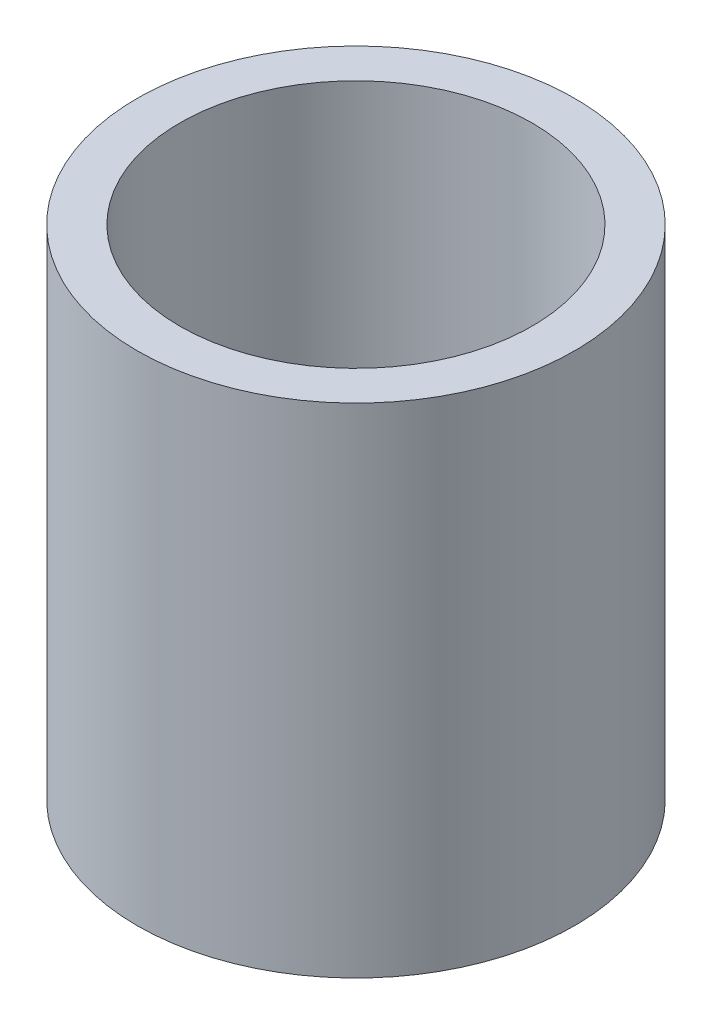
SolidWorks part; units mm, degrees
ref_plane "Front Plane" through (0, 0, 0) normal (0, 0, 1) x (1, 0, 0)
ref_plane "Top Plane" through (0, 0, 0) normal (0, 1, 0) x (1, 0, 0)
ref_plane "Right Plane" through (0, 0, 0) normal (1, 0, 0) x (0, 0, -1)
sketch "Sketch1" plane through (0, 0, 0) normal (0, 1, 0) x (1, 0, 0)
  circle A0 centre (0, 0) radius 27.5
  dimension "SLEEVE_OD" = 55
extrude "Boss-Extrude1" add sketch "Sketch1" along normal blind 62.6106
sketch "Sketch2" plane through (0, 0, 0) normal (0, 1, 0) x (1, 0, 0)
  circle A0 centre (0, 0) radius 22.1463
  dimension "BORE_D" = 44.2925
extrude "Cut-Extrude1" cut sketch "Sketch2" along normal through all
chamfer "Chamfer1" distance 3.4172 angle 60 rebuild error yes
